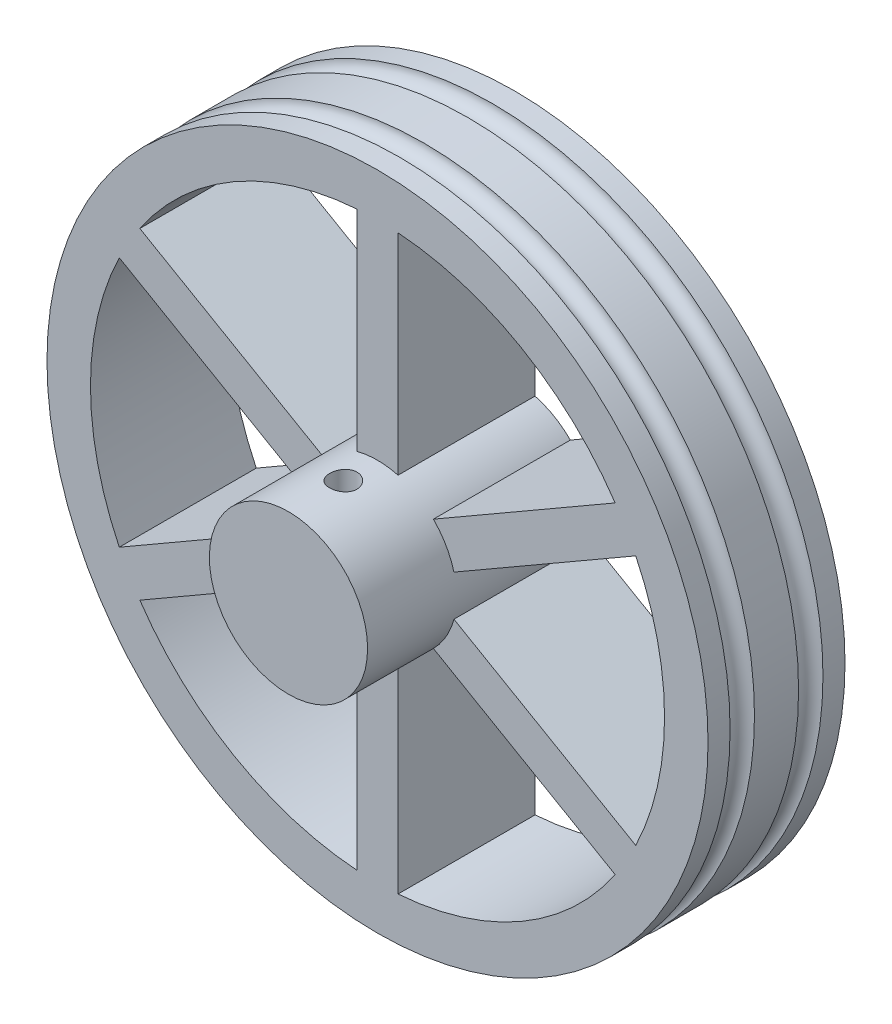
SolidWorks part; units mm, degrees
ref_plane "Front Plane" through (0, 0, 0) normal (0, 0, 1) x (1, 0, 0)
ref_plane "Top Plane" through (0, 0, 0) normal (0, 1, 0) x (1, 0, 0)
ref_plane "Right Plane" through (0, 0, 0) normal (1, 0, 0) x (0, 0, -1)
sketch "Sketch1" plane through (0, 0, 0) normal (0, 0, 1) x (1, 0, 0)
  circle A0 centre (0, 0) radius 24.13
  circle A1 centre (0, 0) radius 20.955
  circle A2 centre (0, 0) radius 2.6
  circle A3 centre (0, 0) radius 5.775
  dimension "D1" = 48.26
  dimension "D2" = 3.175
  dimension "D3" = 5.2
  dimension "D4" = 3.175
extrude "Boss-Extrude1" add sketch "Sketch1" along normal blind 10 contours A0 A1 | A3 A2 region at (-23.4475, 0, 0) region at (-5.6117, 0, 0)
sketch "Sketch3" plane through (0, 0, 0) normal (0, 0, -1) x (-1, 0, 0)
  line L0 (0, 0) -> (0, 2.6) construction
  line L1 (1.5, 2.6) -> (-1.5, 2.6)
  line L2 (0, 2.6) -> (0, 20.955) construction
  line L3 (1.5, 20.955) -> (-1.5, 20.955)
  line L4 (-1.5, 20.955) -> (-1.5, 2.6)
  line L5 (1.5, 20.955) -> (1.5, 2.6)
  circle A0 centre (0, 0) radius 2.6 construction
  circle A1 centre (0, 0) radius 20.955 construction
  point P7 (0, 2.6)
  point P14 (0, 20.955)
  dimension "D1" = 3
  dimension "D2" = 3
extrude "Boss-Extrude3" add sketch "Sketch3" against normal up to surface (10 mm away) up to face at (2.6, 0, 10)
pattern_circular "CirPattern1" count 6 over 360 about axis through (0, 0, 10) along (0, 0, 1) of "Boss-Extrude3"
sketch "Sketch4" plane through (0, 0, 0) normal (1, 0, 0) x (0, 0, -1)
  line L0 (0, 0) -> (0, 24.13) construction
  line L1 (0, 24.13) -> (-10, 24.13) construction
  line L2 (-2.5, 24.13) -> (-7.5, 24.13) construction
  line L3 (0, 0) -> (-22.4846, 0) construction
  circle A0 centre (-7.5, 24.13) radius 0.89
  circle A1 centre (-2.5, 24.13) radius 0.89
  point P9 (-5, 24.13)
  dimension "D3" = 1.78
  dimension "D1" = 10
  dimension "D2" = 5
  dimension "D4" = 24.13
  dimension "D5" = 2.5
revolve "Cut-Revolve1" cut sketch "Sketch4" angle 360 about L3
sketch "Sketch5" plane through (0, 0, 10) normal (0, 0, 1) x (1, 0, 0)
  line L0 (0, 0) -> (0, 2.6) construction
  line L1 (-2.5, 2.6) -> (2.5, 2.6)
  line L2 (-2.5, 2.6) -> (-2.5, 2.1)
  line L3 (2.5, 2.6) -> (2.5, 2.1)
  line L4 (2.5, 2.1) -> (-2.5, 2.1)
  circle A0 centre (0, 0) radius 2.6 construction
  point P9 (0, 2.6)
  dimension "D1" = 5
  dimension "D2" = 0.5
extrude "Boss-Extrude4" add sketch "Sketch5" against normal up to surface (10 mm away) up to face at (6.3951, 11.0766, 0)
ref_plane "Plane2" through (0, 0, 7.5) normal (0, 0, 1) x (1, 0, 0)
ref_plane "Plane3" through (0, 0, 2.5) normal (0, 0, -1) x (-1, 0, 0)
sketch "Sketch6" plane through (0, 0, 10) normal (0, 0, 1) x (1, 0, 0)
  line L0 (-1.533, 2.1) -> (1.533, 2.1)
  circle A0 centre (0, 0) radius 5.775
  arc A1 (-1.533, 2.1) -> (1.533, 2.1) centre (0, 0) ccw
  dimension "D1" = 11.55
extrude "Boss-Extrude5" add sketch "Sketch6" along normal blind 5
sketch "Sketch7" plane through (0, 0, 0) normal (0, 1, 0) x (1, 0, 0)
  line L0 (0, -15) -> (0, -10) construction
  line L2 (-5.775, -15) -> (5.775, -15) construction
  line L3 (-1.5, -10) -> (1.5, -10) construction
  circle A0 centre (0, -12.5) radius 1
  dimension "D1" = 2
extrude "Cut-Extrude1" cut sketch "Sketch7" along normal through all
sketch "Sketch8" plane through (0, 0, 15) normal (0, 0, 1) x (1, 0, 0)
  circle A0 centre (0, 0) radius 5.775
extrude "Boss-Extrude6" add sketch "Sketch8" along normal blind 1.5
